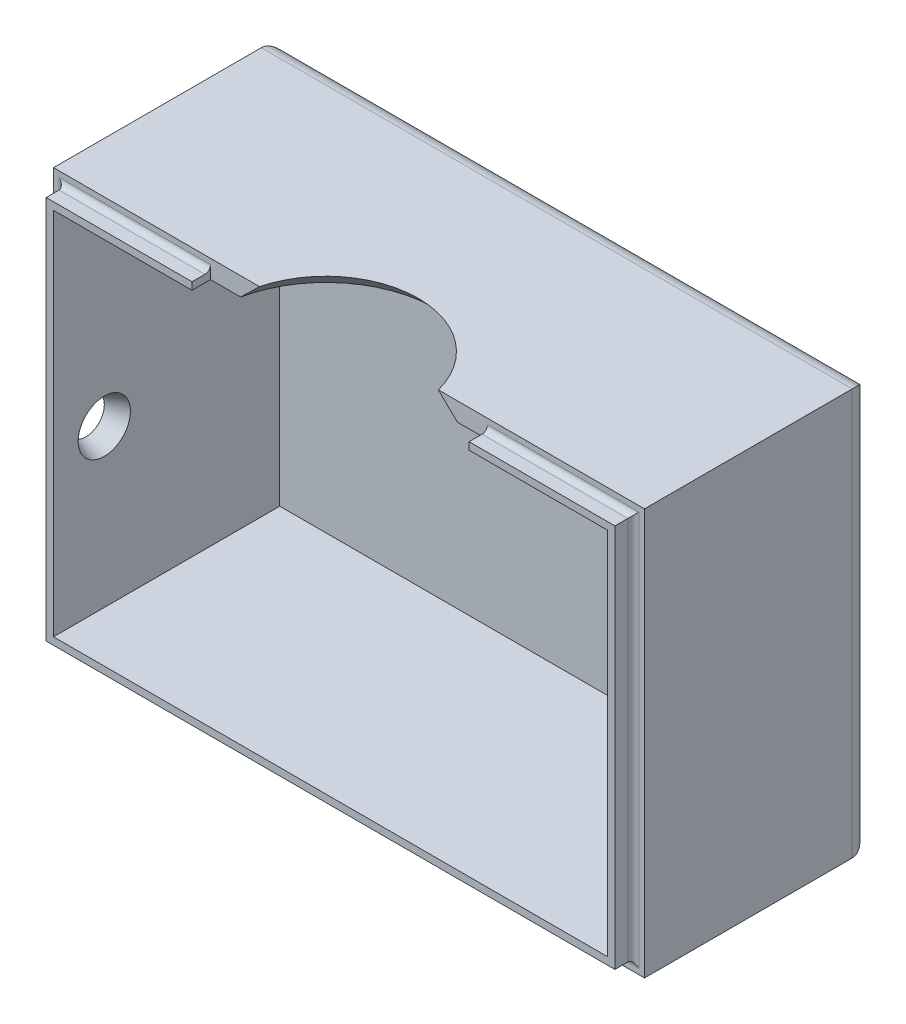
SolidWorks part; units mm, degrees
ref_plane "Front Plane" through (0, 0, 0) normal (0, 0, 1) x (1, 0, 0)
ref_plane "Top Plane" through (0, 0, 0) normal (0, 1, 0) x (1, 0, 0)
ref_plane "Right Plane" through (0, 0, 0) normal (1, 0, 0) x (0, 0, -1)
sketch "Sketch2" plane through (0, 0, 0) normal (0, 0, 1) x (1, 0, 0)
  line L1 (-38.668, 30.4106) -> (37.532, 30.4106)
  line L2 (-38.668, 30.4106) -> (-38.668, -20.3894)
  line L3 (-38.668, -20.3894) -> (37.532, -20.3894)
  line L4 (37.532, 30.4106) -> (37.532, -20.3894)
  line L5 (-41.208, 32.9506) -> (40.072, 32.9506)
  line L6 (-41.208, 32.9506) -> (-41.208, -22.9294)
  line L7 (-41.208, -22.9294) -> (40.072, -22.9294)
  line L8 (40.072, 32.9506) -> (40.072, -22.9294)
  dimension "D1" = 50.8
  dimension "D2" = 76.2
  dimension "D3" = 2.54
  dimension "D4" = 2.54
  dimension "D5" = 2.54
  dimension "D6" = 2.54
extrude "Boss-Extrude1" add sketch "Sketch2" against normal blind 28.575
sketch "Sketch3" plane through (0, 0, -28.575) normal (0, 0, -1) x (-1, 0, 0)
  line L1 (-40.072, 32.9506) -> (41.208, 32.9506)
  line L2 (-40.072, 32.9506) -> (-40.072, -22.9294)
  line L3 (-40.072, -22.9294) -> (41.208, -22.9294)
  line L4 (41.208, 32.9506) -> (41.208, -22.9294)
extrude "Boss-Extrude2" add sketch "Sketch3" along normal blind 2.54
sketch "Sketch6" plane through (-41.208, 0, 0) normal (-1, 0, 0) x (0, 0, 1)
  line L0 (-31.115, -22.9294) -> (0, -22.9294) construction
  line L2 (-31.115, -22.9294) -> (-31.115, 32.9506) construction
  circle A0 centre (-4.445, 1.2006) radius 2.54
  dimension "D1" = 5.08
  dimension "D2" = 24.13
  dimension "D3" = 26.67
extrude "Cut-Extrude2" cut sketch "Sketch6" against normal blind 2.54
chamfer "Chamfer2" distance 2.54 angle 22.5 1 edges at (-38.668, 1.2006, -1.905) first distance on face at (-38.668, 1.2006, -1.905)
sketch "Sketch7" plane through (0, 32.9506, 0) normal (0, 1, 0) x (1, 0, 0)
  line L2 (40.072, 31.115) -> (40.072, 0) construction
  line L3 (40.072, 31.115) -> (-41.208, 31.115) construction
  circle A0 centre (-0.568, -3.175) radius 12.7
  dimension "D1" = 25.4
  dimension "D2" = 34.29
  dimension "D3" = 40.64
extrude "Cut-Extrude5" cut sketch "Sketch7" against normal blind 2.54
sketch "Sketch8" plane through (0, 0, 0) normal (0, 0, 1) x (1, 0, 0)
  line L0 (-38.668, 30.4106) -> (-19.618, 30.4106)
  line L2 (-38.668, 30.4106) -> (-38.668, -20.3894)
  line L3 (-38.668, -20.3894) -> (37.532, -20.3894)
  line L4 (37.532, 30.4106) -> (37.532, -20.3894)
  line L6 (-39.684, 31.4266) -> (-39.684, -21.4054)
  line L7 (-39.684, -21.4054) -> (38.548, -21.4054)
  line L8 (38.548, 31.4266) -> (38.548, -21.4054)
  line L9 (-12.8647, 30.4106) -> (-38.668, 30.4106) construction
  line L10 (-39.684, 31.4266) -> (-19.618, 31.4266)
  line L11 (-19.618, 30.4106) -> (-19.618, 31.4266)
  line L12 (37.532, 30.4106) -> (18.482, 30.4106)
  line L13 (37.532, 30.4106) -> (11.7288, 30.4106) construction
  line L14 (38.548, 31.4266) -> (18.482, 31.4266)
  line L15 (18.482, 31.4266) -> (18.482, 30.4106)
  dimension "D1" = 1.016
  dimension "D2" = 1.016
  dimension "D3" = 1.016
  dimension "D4" = 19.05
  dimension "D5" = 1.016
  dimension "D6" = 19.05
  dimension "D7" = 1.016
extrude "Boss-Extrude3" add sketch "Sketch8" along normal blind 2.54
chamfer "Chamfer3" distance 2.54 angle 45 1 edges at (-0.568, 30.4106, -9.525)
fillet "Fillet2" radius 0.762 5 edges at (-29.651, 31.4266, 0) (-39.684, 5.0106, 0) (-0.568, -21.4054, 0) (38.548, 5.0106, 0) (28.515, 31.4266, 0)
fillet "Fillet3" radius 2.54 4 edges at (40.072, 5.0106, -31.115) (-0.568, -22.9294, -31.115) (-41.208, 5.0106, -31.115) (-0.568, 32.9506, -31.115)
